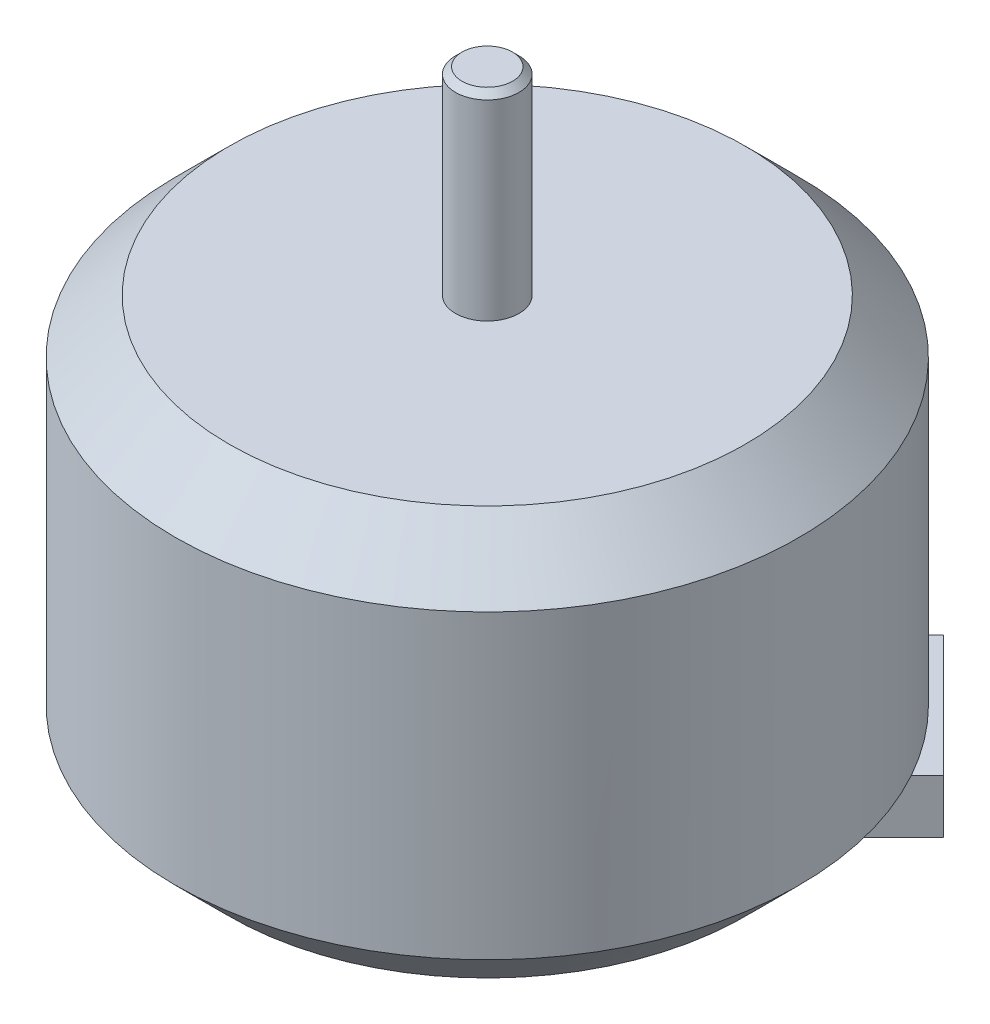
SolidWorks part; units mm, degrees
material "3.0205 (EN-AW 1200)"
ref_plane "Ebene vorne" through (0, 0, 0) normal (0, 0, 1) x (1, 0, 0)
ref_plane "Ebene oben" through (0, 0, 0) normal (0, 1, 0) x (1, 0, 0)
ref_plane "Ebene rechts" through (0, 0, 0) normal (1, 0, 0) x (0, 0, -1)
sketch "Skizze1" plane through (0, 0, 0) normal (0, 1, 0) x (1, 0, 0)
  circle A0 centre (0, 0) radius 14.5
  dimension "D1" = 29
extrude "Grundkoerper" add sketch "Skizze1" along normal blind 19
chamfer "Grundkoerperfase" distance 2.5 angle 45 2 edges at (0, 0, 14.5) (0, 19, 14.5)
sketch "Bohrungsskizze" plane through (0, 0, 0) normal (0, -1, 0) x (1, 0, 0)
  circle A0 centre (0, 0) radius 8 construction
  circle A1 centre (0, 0) radius 9.5 construction
  point P4 (0, 8)
  point P5 (0, -8)
  point P6 (9.5, 0)
  point P7 (-9.5, 0)
  dimension "D1" = 19
  dimension "D2" = 16
hole_wizard "Montagebohrung unten" positions "Skizze3" profile "Skizze4" tap size "M3" standard "DIN"
sketch "Skizze3" plane through (0, 0, 0) normal (0, -1, 0) x (-1, 0, 0)
  point P0 (9.5, 0)
  point P3 (0, -8)
  point P6 (-9.5, 0)
  point P9 (0, 8)
sketch "Skizze4" plane through (-9.5, 0, 0) normal (1, 0, 0) x (0, 0, -1)
  line L0 (0, 0) -> (0, 3.7511)
  line L1 (0, 3.7511) -> (1.25, 3)
  line L2 (1.25, 3) -> (1.25, 0)
  line L5 (1.25, 0) -> (0, 0)
  line L10 (0, 3.7511) -> (-1.25, 3) construction
  line L11 (0, -6.35) -> (0, 107.95) construction
  dimension "Bohrerdurchmesser" = 2.5
  dimension "Bohrungstiefe" = 3
  dimension "Spitzenwinkel" = 118
cosmetic thread "Bohrungsgewinde1" parameters "D1"=3, "D2"=3
cosmetic thread "Bohrungsgewinde2" parameters "D1"=3, "D2"=3
cosmetic thread "Bohrungsgewinde3" parameters "D1"=3, "D2"=3
cosmetic thread "Bohrungsgewinde4" parameters "D1"=3, "D2"=3
sketch "Skizze6" plane through (0, 0, 0) normal (0, 0, 1) x (1, 0, 0)
  line L0 (0, -3.2779) -> (0, 37.7769) construction
  line L2 (12, 19) -> (-12, 19) construction
  line L3 (0, 19) -> (1.475, 19)
  line L4 (0, 19) -> (0, 28.2)
  line L5 (0, 28.2) -> (1.475, 28.2)
  line L6 (1.475, 19) -> (1.475, 28.2)
  line L7 (-12, 0) -> (12, 0) construction
  dimension "D1" = 2.95
  dimension "D2" = 28.2
revolve "Propelleraufnahme" add sketch "Skizze6" angle 360 about L0
chamfer "Aufnahme_Fase" distance 0.3 angle 45 1 edges at (0, 28.2, -1.475)
sketch "Skizze7" plane through (0, 0, 0) normal (0, -1, 0) x (1, 0, 0)
  circle A0 centre (0, 0) radius 3
  dimension "D1" = 6
extrude "Wellenueberstand" add sketch "Skizze7" along normal blind 1
ref_axis "Hilfsachse_Ebene" through (0, -2.25, 0) along (0, 1, 0)
ref_plane "Ebene_Winkelversetzt" through (0, 0, 0) normal (-0.7071, 0, 0.7071) x (0, 1, 0)
ref_plane "Ebene_Kabelanschluss" through (7.0711, 0, -7.0711) normal (-0.7071, 0, 0.7071) x (0, 1, 0)
sketch "Skizze8" plane through (7.0711, 0, -7.0711) normal (-0.7071, 0, 0.7071) x (0, 1, 0)
  line L0 (50.564, 0) -> (-45.4709, 0) construction
  line L1 (-2.25, 0) -> (29.65, 0) construction
  line L2 (0, -18.67) -> (0, 18.67) construction
  line L3 (2.5, -4) -> (0, -4)
  line L4 (2.5, -4) -> (2.5, 4)
  line L5 (2.5, 4) -> (0, 4)
  line L6 (0, -4) -> (0, 4)
  line L7 (2.5, -4) -> (0, 4) construction
  line L8 (2.5, 4) -> (0, -4) construction
  line L9 (2.5, -14.5) -> (2.5, 14.5) construction
  point P5 (1.25, 0)
  dimension "D1" = 8
extrude "Kabelanschluss" add sketch "Skizze8" against normal blind 5
sketch "Skizze_Anschlusspunkte" plane through (10.6066, 0, -10.6066) normal (0.7071, 0, -0.7071) x (-0.7071, 0, -0.7071)
  line L1 (-4, 1.25) -> (4, 1.25) construction
  line L2 (-4, 2.5) -> (-4, 0) construction
  line L3 (4, 2.5) -> (4, 0) construction
  line L4 (0, -3.4208) -> (0, 4.8296) construction
  line L5 (0, -2.25) -> (0, 29.65) construction
  point P6 (0, 1.25)
  point P7 (2.5, 1.25)
  point P8 (-2.5, 1.25)
  dimension "D1" = 2.5
sketch "0_0_Point" plane through (10.6066, 0, -10.6066) normal (0.7071, 0, -0.7071) x (-0.7071, 0, -0.7071)
  point P0 (-2.5, 1.25)
other "0_0" parameters "Durchmesser"=2, "Stumpflänge"=2
ref_axis "Achse1" through (19.4454, 1.25, -15.9099) along (-0.7071, 0, 0.7071)
sketch "0_1_Point" plane through (10.6066, 0, -10.6066) normal (0.7071, 0, -0.7071) x (-0.7071, 0, -0.7071)
  point P0 (0, 1.25)
other "0_1" parameters "Durchmesser"=2, "Stumpflänge"=2
ref_axis "Achse2" through (17.6777, 1.25, -17.6777) along (-0.7071, 0, 0.7071)
sketch "0_2_Point" plane through (10.6066, 0, -10.6066) normal (0.7071, 0, -0.7071) x (-0.7071, 0, -0.7071)
  point P0 (2.5, 1.25)
other "0_2" parameters "Durchmesser"=2, "Stumpflänge"=2
ref_axis "Achse3" through (15.9099, 1.25, -19.4454) along (-0.7071, 0, 0.7071)
